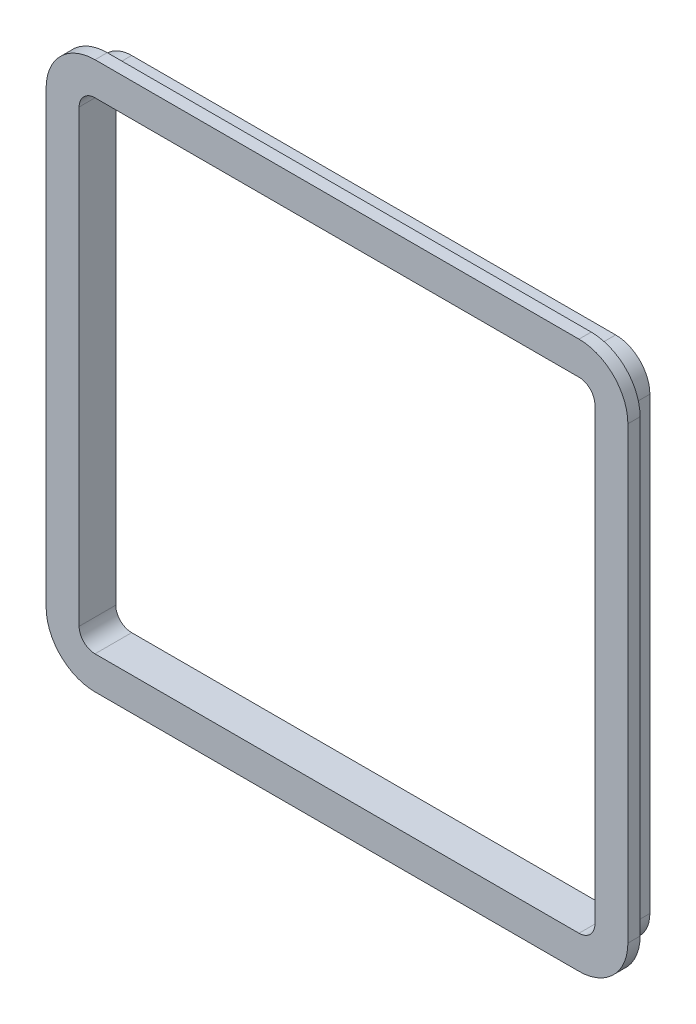
SolidWorks part; units mm, degrees
ref_plane "Front Plane" through (0, 0, 0) normal (0, 0, 1) x (1, 0, 0)
ref_plane "Top Plane" through (0, 0, 0) normal (0, 1, 0) x (1, 0, 0)
ref_plane "Right Plane" through (0, 0, 0) normal (1, 0, 0) x (0, 0, -1)
sketch "Sketch1" plane through (0, 0, 0) normal (0, 0, 1) x (1, 0, 0)
  line L5 (-21.1, 18.4) -> (-21.1, -18.4)
  line L6 (-19.8, -19.7) -> (19.8, -19.7)
  line L7 (21.1, -18.4) -> (21.1, 18.4)
  line L8 (19.8, 19.7) -> (-19.8, 19.7)
  line L9 (22.6, -18.4) -> (22.6, 18.4)
  line L10 (19.8, 21.2) -> (-19.8, 21.2)
  line L11 (-22.6, 18.4) -> (-22.6, -18.4)
  line L12 (-19.8, -21.2) -> (19.8, -21.2)
  line L13 (22.6, -18.4) -> (22.6, 18.4)
  line L14 (19.8, 21.2) -> (-19.8, 21.2)
  line L15 (-22.6, 18.4) -> (-22.6, -18.4)
  line L16 (-19.8, -21.2) -> (19.8, -21.2)
  arc A7 (-19.8, 19.7) -> (-21.1, 18.4) centre (-19.8, 18.4) ccw
  arc A8 (-21.1, -18.4) -> (-19.8, -19.7) centre (-19.8, -18.4) ccw
  arc A9 (19.8, -19.7) -> (21.1, -18.4) centre (19.8, -18.4) ccw
  arc A10 (21.1, 18.4) -> (19.8, 19.7) centre (19.8, 18.4) ccw
  arc A11 (19.8, -21.2) -> (22.6, -18.4) centre (19.8, -18.4) ccw
  arc A12 (22.6, 18.4) -> (19.8, 21.2) centre (19.8, 18.4) ccw
  arc A13 (-19.8, 21.2) -> (-22.6, 18.4) centre (-19.8, 18.4) ccw
  arc A14 (-22.6, -18.4) -> (-19.8, -21.2) centre (-19.8, -18.4) ccw
  arc A15 (19.8, -21.2) -> (22.6, -18.4) centre (19.8, -18.4) ccw
  arc A16 (22.6, 18.4) -> (19.8, 21.2) centre (19.8, 18.4) ccw
  arc A17 (-19.8, 21.2) -> (-22.6, 18.4) centre (-19.8, 18.4) ccw
  arc A18 (-22.6, -18.4) -> (-19.8, -21.2) centre (-19.8, -18.4) ccw
  dimension "D1" = 0.2
  dimension "D2" = 1.5
extrude "Boss-Extrude1" add sketch "Sketch1" along normal up to surface (2 mm away)
sketch "Sketch2" plane through (0, 0, 2) normal (0, 0, 1) x (1, 0, 0)
  line L0 (-19.8, -19.7) -> (19.8, -19.7) construction
  line L1 (21.1, -18.4) -> (21.1, 18.4) construction
  line L2 (19.8, 19.7) -> (-19.8, 19.7) construction
  line L3 (-21.1, 18.4) -> (-21.1, -18.4) construction
  line L4 (-19.8, -22.4) -> (19.8, -22.4)
  line L5 (23.8, -18.4) -> (23.8, 18.4)
  line L6 (19.8, 22.4) -> (-19.8, 22.4)
  line L7 (-23.8, 18.4) -> (-23.8, -18.4)
  line L8 (-19.8, -22.4) -> (19.8, -22.4)
  line L9 (23.8, -18.4) -> (23.8, 18.4)
  line L10 (19.8, 22.4) -> (-19.8, 22.4)
  line L11 (-23.8, 18.4) -> (-23.8, -18.4)
  line L12 (-19.8, -19.7) -> (19.8, -19.7)
  line L13 (21.1, -18.4) -> (21.1, 18.4)
  line L14 (19.8, 19.7) -> (-19.8, 19.7)
  line L15 (-21.1, 18.4) -> (-21.1, -18.4)
  arc A0 (-21.1, -18.4) -> (-19.8, -19.7) centre (-19.8, -18.4) ccw construction
  arc A1 (19.8, -19.7) -> (21.1, -18.4) centre (19.8, -18.4) ccw construction
  arc A2 (21.1, 18.4) -> (19.8, 19.7) centre (19.8, 18.4) ccw construction
  arc A3 (-19.8, 19.7) -> (-21.1, 18.4) centre (-19.8, 18.4) ccw construction
  arc A4 (-23.8, -18.4) -> (-19.8, -22.4) centre (-19.8, -18.4) ccw
  arc A5 (19.8, -22.4) -> (23.8, -18.4) centre (19.8, -18.4) ccw
  arc A6 (23.8, 18.4) -> (19.8, 22.4) centre (19.8, 18.4) ccw
  arc A7 (-19.8, 22.4) -> (-23.8, 18.4) centre (-19.8, 18.4) ccw
  arc A8 (-23.8, -18.4) -> (-19.8, -22.4) centre (-19.8, -18.4) ccw
  arc A9 (19.8, -22.4) -> (23.8, -18.4) centre (19.8, -18.4) ccw
  arc A10 (23.8, 18.4) -> (19.8, 22.4) centre (19.8, 18.4) ccw
  arc A11 (-19.8, 22.4) -> (-23.8, 18.4) centre (-19.8, 18.4) ccw
  arc A12 (-21.1, -18.4) -> (-19.8, -19.7) centre (-19.8, -18.4) ccw
  arc A13 (19.8, -19.7) -> (21.1, -18.4) centre (19.8, -18.4) ccw
  arc A14 (21.1, 18.4) -> (19.8, 19.7) centre (19.8, 18.4) ccw
  arc A15 (-19.8, 19.7) -> (-21.1, 18.4) centre (-19.8, 18.4) ccw
  dimension "D1" = 0
extrude "Boss-Extrude2" add sketch "Sketch2" along normal blind 1
